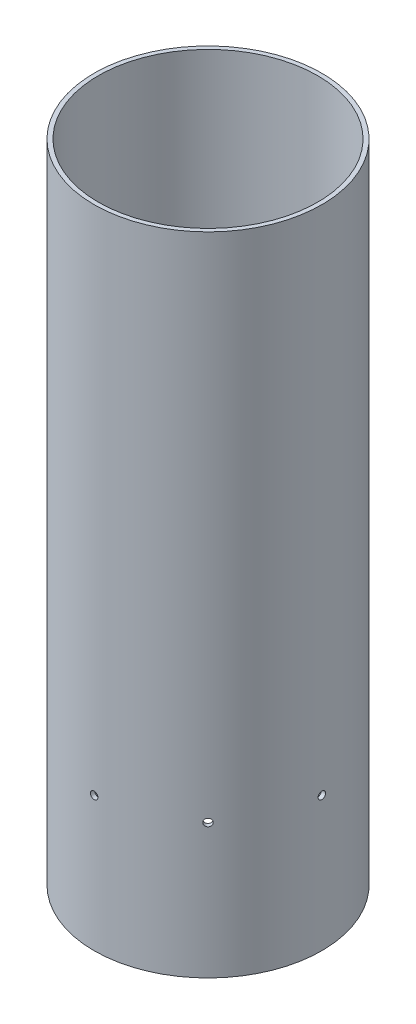
SolidWorks part; units mm, degrees
material "E-Glass Fiber"
ref_plane "Front Plane" through (0, 0, 0) normal (0, 0, 1) x (1, 0, 0)
ref_plane "Top Plane" through (0, 0, 0) normal (0, 1, 0) x (1, 0, 0)
ref_plane "Right Plane" through (0, 0, 0) normal (1, 0, 0) x (0, 0, -1)
sketch "Sketch1" plane through (0, 0, 0) normal (0, 1, 0) x (1, 0, 0)
  circle A0 centre (0, 0) radius 53.721
  circle A1 centre (0, 0) radius 51.7271
  dimension "D1" = 107.442
  dimension "D2" = 103.4542
extrude "Boss-Extrude1" add sketch "Sketch1" along normal blind 304.8
sketch "Sketch2" plane through (0, 0, 0) normal (0, 0, 1) x (1, 0, 0)
  line L2 (0, 0) -> (0, 63.5)
  circle A0 centre (0, 63.5) radius 1.7526
  dimension "D2" = 3.5052
  dimension "D1" = 63.5
extrude "Cut-Extrude2" cut sketch "Sketch2" against normal blind 127 contours A0
pattern_circular "CirPattern1" count 8 over 360 about axis through (0, 304.8, 0) along (0, -1, 0) of "Cut-Extrude2" reverse direction yes
